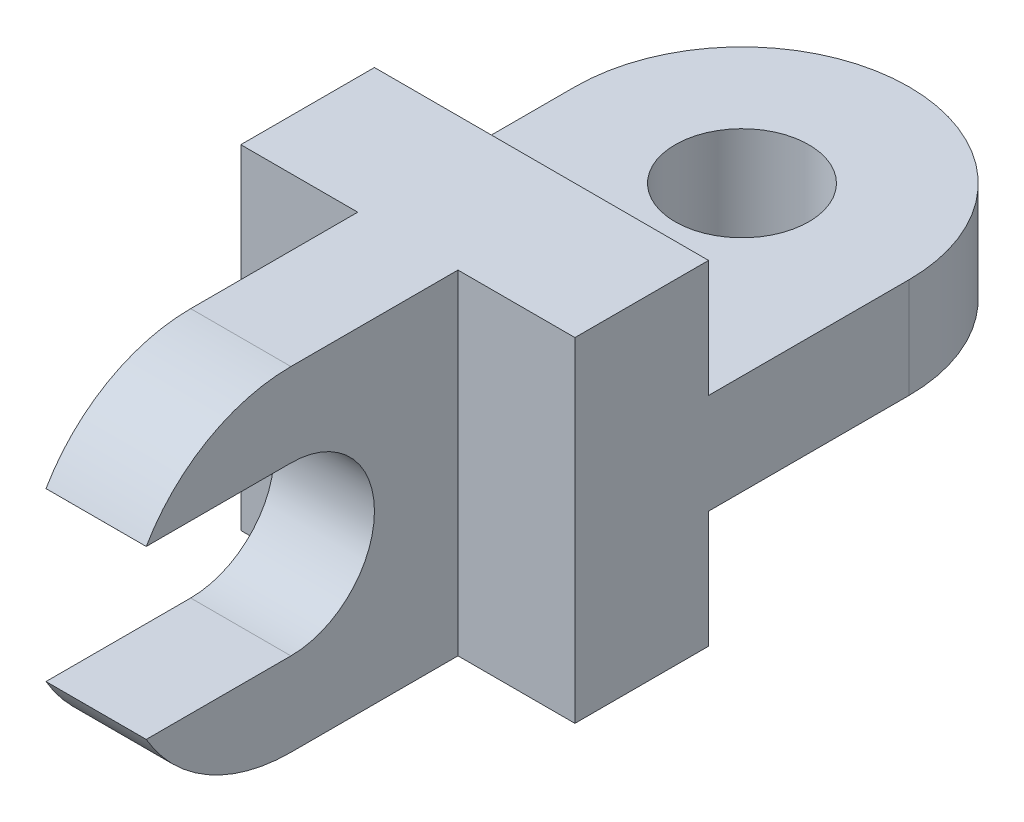
SolidWorks part; units mm, degrees
ref_plane "Front Plane" through (0, 0, 0) normal (0, 0, 1) x (1, 0, 0)
ref_plane "Top Plane" through (0, 0, 0) normal (0, 1, 0) x (1, 0, 0)
ref_plane "Right Plane" through (0, 0, 0) normal (1, 0, 0) x (0, 0, -1)
sketch "Sketch1" plane through (0, 0, 0) normal (0, 1, 0) x (1, 0, 0)
  line L0 (-50, 0) -> (-50, -100)
  line L1 (-15, -100) -> (-15, -193.3)
  line L2 (-50, -100) -> (-15, -100)
  line L3 (0, 0) -> (0, -193.3) construction
  line L4 (-15, -193.3) -> (15, -193.3)
  line L5 (15, -100) -> (15, -193.3)
  line L6 (50, -100) -> (15, -100)
  line L7 (50, 0) -> (50, -100)
  line L8 (-50, -60) -> (50, -60)
  arc A0 (50, 0) -> (-50, 0) centre (0, 0) ccw
  circle A1 centre (0, 0) radius 20
  dimension "D1" = 100
  dimension "D4" = 193.3
  dimension "D6" = 40
  dimension "D2" = 100
  dimension "D3" = 35
  dimension "D5" = 60
extrude "Boss-Extrude1" add sketch "Sketch1" along normal mid plane 30 contours L7 A0 L0 L8 region at (0, 0, -48.5134)
extrude "Boss-Extrude2" add sketch "Sketch1<3>" along normal mid plane 100 contours L3 L8 L0 L2 L1 L4 | L8 L3 L4 L5 L6 L7 region at (-25, 0, 61.4237) region at (25, 0, 61.4237)
sketch "Sketch1<3>" plane through (0, 0, 0) normal (0, 1, 0) x (1, 0, 0) same geometry as "Sketch1"
sketch "Sketch2" plane through (15, 0, 0) normal (1, 0, 0) x (0, 0, -1)
  line L0 (50, -15) -> (50, 15) construction
  line L1 (-150, 25) -> (-193.3, 25)
  line L2 (-193.3, 50) -> (-193.3, -50) construction
  line L3 (-193.3, 25) -> (-193.3, -25)
  line L4 (-150, -25) -> (-193.3, -25)
  line L9 (-193.3, -50) -> (-100, -50)
  line L10 (-100, -50) -> (-100, 50)
  line L11 (-100, 50) -> (-193.3, 50)
  line L12 (-193.3, 50) -> (-193.3, -50)
  line L13 (-193.3, -50) -> (-150, -50)
  line L15 (-150, 50) -> (-193.3, 50)
  line L16 (-193.3, 50) -> (-193.3, -50)
  arc A0 (-150, -25) -> (-150, 25) centre (-150, 0) ccw
  arc A1 (-150, 50) -> (-193.3, 25.0022) centre (-150, 0) ccw
  arc A2 (-193.3, -25.0022) -> (-150, -50) centre (-150, 0) ccw
  line M5 (-193.3, -50) -> (-100, -50)
  line M7 (-100, 50) -> (-193.3, 50)
  line M8 (-193.3, 50) -> (-193.3, -50)
  dimension "D1" = 50
  dimension "D2" = 200
  dimension "D3" = 100
  dimension "D4" = 0
extrude "Cut-Extrude1" cut sketch "Sketch2" against normal through all contours A1 M7 M8 | L4 A0 L1 M8 | A2 L16 M5 region at (15, 0, 161.5852) region at (15, 42.9854, 183.0887) region at (15, -42.9854, 183.0887)
